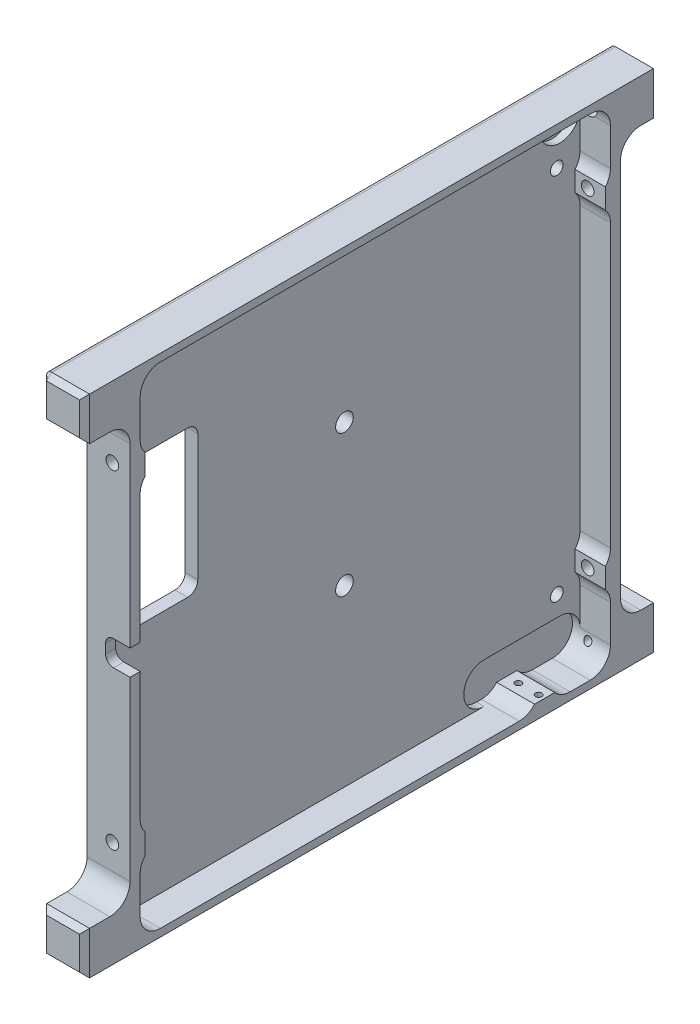
SolidWorks part; units mm, degrees
material "6061-T6 (SS)"
ref_plane "Front" through (0, 0, 0) normal (0, 0, 1) x (1, 0, 0)
ref_plane "Top" through (0, 0, 0) normal (0, 1, 0) x (1, 0, 0)
ref_plane "Right" through (0, 0, 0) normal (1, 0, 0) x (0, 0, -1)
sketch "Sketch1" plane through (0, 0, 0) normal (1, 0, 0) x (0, 0, -1)
  line L1 (0, 0) -> (-113.5, 0)
  line L2 (0, 0) -> (0, 100)
  line L3 (0, 100) -> (-113.5, 100)
  line L4 (-113.5, 0) -> (-113.5, 100)
  line L5 (-113.5, 91.5) -> (-104.5, 91.5)
  line L6 (-113.5, 91.5) -> (-113.5, 8.5)
  line L7 (-113.5, 8.5) -> (-104.5, 8.5)
  line L8 (-104.5, 91.5) -> (-104.5, 8.5)
  line L9 (0, 91.5) -> (-7.5, 91.5)
  line L10 (0, 91.5) -> (0, 8.5)
  line L11 (0, 8.5) -> (-7.5, 8.5)
  line L12 (-7.5, 91.5) -> (-7.5, 8.5)
  line L13 (-96.5, 91.5) -> (-15.5, 91.5)
  line L14 (-96.5, 91.5) -> (-96.5, 8.5)
  line L15 (-96.5, 8.5) -> (-15.5, 8.5)
  line L16 (-15.5, 91.5) -> (-15.5, 8.5)
  dimension "D1" = 113.5
  dimension "D2" = 100
  dimension "D3" = 8.5
  dimension "D4" = 8.5
  dimension "D5" = 8
  dimension "D6" = 8
  dimension "D7" = 9
  dimension "D8" = 7.5
extrude "Body" add sketch "Sketch1" along normal blind 8.5 contours L12 L9 L2 L3 L4 L5 L8 L7 L1 L11 L13 L16 L15 L14
fillet "RailFillet" radius 1 2 edges at (0, 0, 56.75) (0, 100, 56.75)
chamfer "FootChamfer" distance 1 angle 45 20 edges at (4.75, 0, 0) (8.5, 4.25, 0) (4.25, 8.5, 0) (0, 4.75, 0) (4.25, 91.5, 0) (8.5, 95.75, 0) (4.75, 100, 0) (0, 95.25, 0) (4.75, 100, 113.5) (8.5, 95.75, 113.5) (4.25, 91.5, 113.5) (0, 95.25, 113.5) (4.25, 8.5, 113.5) (8.5, 4.25, 113.5) (4.75, 0, 113.5) (0, 4.75, 113.5) (0.2929, 0.2929, 0) (0.2929, 99.7071, 0) (0.2929, 99.7071, 113.5) (0.2929, 0.2929, 113.5)
sketch "Sketch5" plane through (8.5, 0, 0) normal (1, 0, 0) x (0, 0, -1)
  line L1 (-96.5, 91.5) -> (-15.5, 91.5)
  line L2 (-96.5, 91.5) -> (-96.5, 8.5)
  line L3 (-96.5, 8.5) -> (-15.5, 8.5)
  line L4 (-15.5, 91.5) -> (-15.5, 8.5)
extrude "Boss-Extrude3" add sketch "Sketch5" against normal up to surface (8.5 mm away) up to face at (0, 50, 56.5)
sketch "Sketch6" plane through (8.5, 0, 0) normal (1, 0, 0) x (0, 0, -1)
  line L0 (-1, 100) -> (-112.5, 100) construction
  line L1 (-102.5, 98.5) -> (-9.5, 98.5)
  line L2 (-102.5, 98.5) -> (-102.5, 1.5)
  line L3 (-102.5, 1.5) -> (-9.5, 1.5)
  line L4 (-9.5, 98.5) -> (-9.5, 1.5)
  line L5 (-1, 0) -> (-112.5, 0) construction
  line L7 (-7.5, 91.5) -> (-7.5, 8.5) construction
  line L10 (-104.5, 91.5) -> (-104.5, 8.5) construction
  dimension "D1" = 1.5
  dimension "D2" = 1.5
  dimension "D3" = 2
  dimension "D4" = 2
extrude "Cut-Extrude3" cut sketch "Sketch6" against normal offset from surface (6 mm away) 2.5 up to face at (0, 50, 56.5)
sketch "Sketch4" plane through (8.5, 0, 0) normal (1, 0, 0) x (0, 0, -1)
  line L1 (-92.5, 90) -> (-19.5, 90)
  line L2 (-92.5, 90) -> (-92.5, 10)
  line L3 (-92.5, 10) -> (-19.5, 10)
  line L4 (-19.5, 90) -> (-19.5, 10)
  line L6 (-7.5, 91.5) -> (-7.5, 8.5) construction
  line L8 (-1, 100) -> (-112.5, 100) construction
  line L9 (-1, 0) -> (-112.5, 0) construction
  line L10 (-104.5, 91.5) -> (-104.5, 8.5) construction
  dimension "D1" = 12
  dimension "D2" = 10
  dimension "D3" = 10
  dimension "D4" = 12
ref_plane "Plane1" through (0, 50, 0) normal (0, 1, 0) x (1, 0, 0)
ref_plane "Plane2" through (0, 0, 56) normal (0, 0, -1) x (-1, 0, 0)
sketch "Sketch21" plane through (0, 0, 0) normal (1, 0, 0) x (0, 0, -1)
  line L0 (-98.1, 86.5) -> (-98.1, 13.5) construction
  line L1 (-98.1, 13.5) -> (-14.1, 13.5) construction
  line L2 (-14.1, 13.5) -> (-14.1, 86.5) construction
  line L3 (-14.1, 86.5) -> (-98.1, 86.5) construction
  line L4 (-14.1, 50) -> (-7.5, 50) construction
  line L6 (-7.5, 91.5) -> (-7.5, 8.5) construction
  line L7 (0, 99) -> (0, 92.5) construction
  line L8 (-14.1, 50) -> (-98.1, 50) construction
  line L9 (-56.1, 50) -> (-56.1, 36) construction
  line L10 (-7.5, 50) -> (-7.5, 0) construction
  line L11 (-112.5, 0) -> (-1, 0) construction
  line L12 (-1, 100) -> (-112.5, 100) construction
  line L13 (-7.5, 100) -> (-7.5, 50) construction
  line L16 (-56.1, 64) -> (-56.1, 50) construction
  point P3 (-14.1, 13.5)
  point P5 (-98.1, 86.5)
  point P7 (-98.1, 13.5)
  point P11 (-56.1, 36)
  point P25 (-14.1, 86.5)
  point P26 (-56.1, 64)
  dimension "D3" = 28
  dimension "D1" = 73
  dimension "D2" = 84
  dimension "D4" = 14.1
sketch "Sketch29" plane through (0, 0, 0) normal (0, 0, -1) x (-1, 0, 0)
  line L0 (-1, 92.5) -> (-7.5, 99)
  line L1 (-7.5, 99) -> (-1, 99)
  line L2 (-1, 99) -> (-4.25, 95.75)
hole_wizard "#8-36 Tapped Hole1" positions "Sketch30" profile "Sketch31" tap size "#8-36" standard "ANSI Inch"
sketch "Sketch30" plane through (0, 0, 0) normal (0, 0, -1) x (-1, 0, 0)
  point P0 (-4.25, 95.75)
sketch "Sketch31" plane through (4.25, 95.75, 0) normal (1, 0, 0) x (0, 1, 0)
  line L0 (0, 0) -> (0, 14.5878)
  line L1 (0, 14.5878) -> (1.7272, 13.55)
  line L2 (1.7272, 13.55) -> (1.7272, 0)
  line L5 (1.7272, 0) -> (0, 0)
  line L10 (0, 14.5878) -> (-1.7272, 13.55) construction
  line L11 (0, -6.35) -> (0, 107.95) construction
  dimension "Tap Drill Dia." = 3.4544
  dimension "Tap Drill Depth" = 13.55
  dimension "Drill Angle" = 118
cosmetic thread "Hole Thread1" parameters "D1"=10.5229, "D2"=4.1656
sketch "Sketch32" plane through (0, 0, 0) normal (0, 0, -1) x (-1, 0, 0)
  line L1 (-4.25, 1) -> (-4.25, 4.25) construction
  line L2 (-7.5, 1) -> (-1, 1) construction
  line L3 (-4.25, 4.25) -> (-7.5, 4.25) construction
  line L4 (-7.5, 7.5) -> (-7.5, 1) construction
  point P1 (-4.25, 4.25)
hole_wizard "#8-36 Tapped Hole2" [suppressed] positions "Sketch33" profile "Sketch34" tap size "#8-36" standard "ANSI Inch"
sketch "Sketch33" plane through (0, 0, 0) normal (0, 0, -1) x (-1, 0, 0)
  point P0 (-4.25, 4.25)
sketch "Sketch34" plane through (4.25, 4.25, 0) normal (1, 0, 0) x (0, 1, 0)
  line L0 (0, 0) -> (0, 11.4878)
  line L1 (0, 11.4878) -> (1.7272, 10.45)
  line L2 (1.7272, 10.45) -> (1.7272, 0)
  line L5 (1.7272, 0) -> (0, 0)
  line L10 (0, 11.4878) -> (-1.7272, 10.45) construction
  line L11 (0, -6.35) -> (0, 107.95) construction
  dimension "Tap Drill Dia." = 3.4544
  dimension "Tap Drill Depth" = 10.45
  dimension "Drill Angle" = 118
cosmetic thread "Hole Thread2" [suppressed] parameters "D1"=8.33, "D2"=4.1656
sketch "Sketch44" [suppressed] plane through (2.5, 0, 0) normal (1, 0, 0) x (0, 0, -1)
  point P0 (-17.45, 3.7)
  point P2 (-17.45, 7.7)
sketch "Sketch57" plane through (2.5, 0, 0) normal (1, 0, 0) x (0, 0, -1)
  line L0 (-9.5, 1.5) -> (-9.5, 98.5) construction
  line L1 (-9.5, 84.5) -> (-10.5, 84.5)
  line L2 (-9.5, 84.5) -> (-9.5, 80.5)
  line L3 (-9.5, 80.5) -> (-10.5, 80.5)
  line L4 (-10.5, 84.5) -> (-10.5, 80.5)
  line L5 (-102.5, 1.5) -> (-102.5, 98.5) construction
  line L6 (-9.5, 19.5) -> (-10.5, 19.5)
  line L7 (-9.5, 19.5) -> (-9.5, 15.5)
  line L8 (-9.5, 15.5) -> (-10.5, 15.5)
  line L9 (-10.5, 19.5) -> (-10.5, 15.5)
  line L10 (-10.5, 19.5) -> (-101.5, 19.5)
  line L11 (-10.5, 19.5) -> (-10.5, 15.5)
  line L12 (-10.5, 15.5) -> (-101.5, 15.5)
  line L13 (-101.5, 19.5) -> (-101.5, 15.5)
  line L14 (-10.5, 84.5) -> (-101.5, 84.5)
  line L15 (-10.5, 84.5) -> (-10.5, 80.5)
  line L16 (-10.5, 80.5) -> (-101.5, 80.5)
  line L17 (-101.5, 84.5) -> (-101.5, 80.5)
  line L18 (-101.5, 84.5) -> (-102.5, 84.5)
  line L19 (-101.5, 84.5) -> (-101.5, 80.5)
  line L20 (-101.5, 80.5) -> (-102.5, 80.5)
  line L21 (-102.5, 84.5) -> (-102.5, 80.5)
  line L22 (-9.5, 50) -> (-102.5, 50) construction
  line L23 (-101.5, 19.5) -> (-102.5, 19.5)
  line L24 (-101.5, 19.5) -> (-101.5, 15.5)
  line L25 (-101.5, 15.5) -> (-102.5, 15.5)
  line L26 (-102.5, 19.5) -> (-102.5, 15.5)
  line L28 (-102.5, 82.5) -> (-102.5, 50) construction
  line L29 (-102.5, 50) -> (-102.5, 17.5) construction
  line L31 (-9.5, 98.5) -> (-9.5, 1.5) construction
  dimension "D1" = 4
  dimension "D2" = 4
  dimension "D3" = 1
  dimension "D4" = 32.5
  dimension "D5" = 32.5
extrude "Boss-Extrude24" add sketch "Sketch57" along normal up to surface (6 mm away) contours L18 L21 L20 L17 | L23 L26 L25 L13 | L6 L9 L8 L7 | L1 L4 L3 L2 up to face at (8.5, 50, 56)
fillet "Fillet5" radius 4 8 edges at (5.5, 84.5, 102.5) (5.5, 19.5, 102.5) (5.5, 80.5, 102.5) (5.5, 15.5, 102.5) (5.5, 19.5, 9.5) (5.5, 15.5, 9.5) (5.5, 80.5, 9.5) (5.5, 84.5, 9.5)
sketch "Sketch59" plane through (0, 0, 7.5) normal (0, 0, -1) x (-1, 0, 0)
  line L0 (-5, 91.5) -> (-5, 82.5) construction
  line L2 (-5, 82.5) -> (-5, 17.5) construction
  line L3 (-5, 17.5) -> (-5, 8.5) construction
  line L5 (0, 91.5) -> (0, 8.5) construction
  line L6 (-8.5, 91.5) -> (0, 91.5) construction
  line L7 (-8.5, 8.5) -> (0, 8.5) construction
  dimension "D1" = 65
  dimension "D2" = 5
hole_wizard "M3x0.5 Tapped Hole1" positions "Sketch60" profile "Sketch61" tap size "M3x0.5" standard "ANSI Metric" end condition through all
sketch "Sketch60" plane through (0, 0, 7.5) normal (0, 0, -1) x (-1, 0, 0)
  point P0 (-5, 82.5)
  point P3 (-5, 17.5)
sketch "Sketch61" plane through (5, 82.5, 7.5) normal (1, 0, 0) x (0, 1, 0)
  line L0 (0, 0) -> (0, 106)
  line L1 (0, 106) -> (1.25, 106)
  line L2 (1.25, 106) -> (1.25, 0)
  line L5 (1.25, 0) -> (0, 0)
  line L11 (0, -6.35) -> (0, 107.95) construction
  dimension "Thru Tap Drill Dia." = 2.5
  dimension "Thru Tap Drill Depth" = 106
cosmetic thread "Hole Thread5" parameters "D2"=3
cosmetic thread "Hole Thread6" parameters "D2"=3
sketch "Sketch62" [suppressed] plane through (1, 0, 0) normal (1, 0, 0) x (0, 0, -1)
  line L1 (-11.25, 13.5) -> (-11.25, 1.5)
  line L2 (-11.5, 1.5) -> (-100, 1.5) construction
  line L3 (-11.25, 1.5) -> (-15.75, 1.5)
  line L4 (-15.75, 1.5) -> (-15.75, 10.1459)
  circle A0 centre (-14.75, 86.5) radius 3.5
  circle A1 centre (-14.75, 13.5) radius 3.5
  circle A2 centre (-97.75, 13.5) radius 3.5
  circle A3 centre (-97.75, 86.5) radius 3.5
  circle A4 centre (-97.75, 86.5) radius 1.25 construction
  circle A5 centre (-97.75, 13.5) radius 1.25 construction
  circle A6 centre (-14.75, 13.5) radius 1.25 construction
  circle A7 centre (-14.75, 86.5) radius 1.25 construction
  circle A8 centre (-97.75, 86.5) radius 1.25
  circle A9 centre (-97.75, 13.5) radius 1.25
  circle A10 centre (-14.75, 13.5) radius 1.25
  circle A11 centre (-14.75, 86.5) radius 1.25
  dimension "D1" = 7
  dimension "D2" = 4.5
fillet "Fillet7" radius 4 4 edges at (5.5, 98.5, 102.5) (5.5, 1.5, 102.5) (5.5, 1.5, 9.5) (5.5, 98.5, 9.5)
hole_wizard "M3x0.5 Tapped Hole2" positions "Sketch67" profile "Sketch68" tap size "M3x0.5" standard "ANSI Metric"
sketch "Sketch67" plane through (0, 0, 0) normal (-1, 0, 0) x (0, 0, 1)
  point P0 (14.1, 13.5)
  point P3 (14.1, 86.5)
  point P12 (98.1, 86.5)
  point P15 (98.1, 13.5)
sketch "Sketch68" plane through (0, 13.5, 14.1) normal (0, 1, 0) x (0, 0, 1)
  line L0 (0, 0) -> (0, 8.2511)
  line L1 (0, 8.2511) -> (1.25, 7.5)
  line L2 (1.25, 7.5) -> (1.25, 0)
  line L5 (1.25, 0) -> (0, 0)
  line L10 (0, 8.2511) -> (-1.25, 7.5) construction
  line L11 (0, -6.35) -> (0, 107.95) construction
  dimension "Tap Drill Dia." = 2.5
  dimension "Tap Drill Depth" = 7.5
  dimension "Drill Angle" = 118
cosmetic thread "Hole Thread17" parameters "D1"=2.5, "D2"=3
cosmetic thread "Hole Thread18" parameters "D1"=2.5, "D2"=3
cosmetic thread "Hole Thread21" parameters "D1"=2.5, "D2"=3
cosmetic thread "Hole Thread22" parameters "D1"=2.5, "D2"=3
fillet "Fillet8" radius 4 4 edges at (4.25, 8.5, 104.5) (4.25, 91.5, 104.5) (4.25, 8.5, 7.5) (4.25, 91.5, 7.5)
sketch "Sketch70" plane through (2.5, 0, 0) normal (1, 0, 0) x (0, 0, -1)
  line L0 (-13.5, 1.5) -> (-98.5, 1.5) construction
  line L2 (-13.5, 9.5) -> (-28.5, 9.5)
  line L4 (-13.5, 5.5) -> (-28.5, 5.5) construction
  line L5 (-28.5, 1.5) -> (-13.5, 1.5)
  circle A0 centre (-13.5, 94.5) radius 4
  arc A1 (-9.5, 94.5) -> (-13.5, 98.5) centre (-13.5, 94.5) ccw construction
  circle A2 centre (-13.5, 5.5) radius 4
  circle A3 centre (-28.5, 5.5) radius 4
  dimension "D1" = 15
extrude "Cut-Extrude14" cut sketch "Sketch70" against normal blind 1.5
sketch "Sketch75" plane through (0, 1.5, 0) normal (0, 1, 0) x (1, 0, 0)
  line L0 (1, -28.5) -> (1, -13.5) construction
  line L1 (1, -20.5) -> (8.5, -20.5)
  line L2 (1, -20.5) -> (1, -24.5)
  line L3 (1, -24.5) -> (8.5, -24.5)
  line L4 (8.5, -20.5) -> (8.5, -24.5)
  line L5 (8.5, -98.5) -> (8.5, -13.5) construction
  line L6 (8.5, -13.5) -> (1, -13.5) construction
  dimension "D1" = 7
  dimension "D2" = 4
extrude "Boss-Extrude25" add sketch "Sketch75" along normal blind 1.4
sketch "Sketch71" plane through (0, 2.9, 0) normal (0, 1, 0) x (1, 0, 0)
  line L0 (3.3, -22.5) -> (7.3, -22.5) construction
  line L1 (1, -28.5) -> (1, -24.5) construction
  dimension "D1" = 4
  dimension "D2" = 2.3
  dimension "D3" = 9
hole_wizard "M1.6x0.35 Tapped Hole1" positions "Sketch72" profile "Sketch73" tap size "M1.6x0.35" standard "ANSI Metric"
sketch "Sketch72" plane through (0, 2.9, 0) normal (0, 1, 0) x (1, 0, 0)
  point P0 (3.3, -22.5)
  point P3 (7.3, -22.5)
sketch "Sketch73" plane through (3.3, 2.9, 22.5) normal (1, 0, 0) x (0, 0, 1)
  line L0 (0, 0) -> (0, 4.6255)
  line L1 (0, 4.6255) -> (0.625, 4.25)
  line L2 (0.625, 4.25) -> (0.625, 0)
  line L5 (0.625, 0) -> (0, 0)
  line L10 (0, 4.6255) -> (-0.625, 4.25) construction
  line L11 (0, -6.35) -> (0, 107.95) construction
  dimension "Tap Drill Dia." = 1.25
  dimension "Tap Drill Depth" = 4.25
  dimension "Drill Angle" = 118
cosmetic thread "Hole Thread15" parameters "D1"=1.5, "D2"=1.6
cosmetic thread "Hole Thread16" parameters "D1"=1.5, "D2"=1.6
fillet "Fillet9" radius 4 2 edges at (4.75, 1.5, 24.5) (4.75, 1.5, 20.5)
sketch "Sketch76" plane through (0, 0, 0) normal (0, 0, -1) x (-1, 0, 0)
  line L0 (-1, 7.5) -> (-7.5, 1) construction
  point P4 (-4.25, 4.25)
hole_wizard "Ø1.5mm Dowel Hole1" positions "Sketch77" profile "Sketch79" hole size "Ø1.5" standard "ANSI Metric" end condition up to next
sketch "Sketch77" plane through (0, 0, 0) normal (0, 0, -1) x (-1, 0, 0)
  point P0 (-4.25, 4.25)
sketch "Sketch79" plane through (4.25, 4.25, 0) normal (1, 0, 0) x (0, 1, 0)
  line L0 (0, 0) -> (0, 9.7003)
  line L1 (0, 9.7003) -> (0.75, 9.7003)
  line L2 (0.75, 9.7003) -> (0.75, 0)
  line L5 (0.75, 0) -> (0, 0)
  line L11 (0, -6.35) -> (0, 107.95) construction
  dimension "Thru Hole Dia." = 1.5
  dimension "Thru Hole Depth" = 9.7003
sketch "Sketch81" plane through (2.5, 0, 0) normal (1, 0, 0) x (0, 0, -1)
  line L0 (-87.1, 51.5) -> (-87.1, 76.5) construction
  line L1 (-89.1, 51.5) -> (-89.1, 76.5)
  line L2 (-85.1, 51.5) -> (-85.1, 76.5)
  line L3 (-100.5, 51.5) -> (-100.5, 76.5) construction
  line L4 (-102.5, 51.5) -> (-102.5, 76.5)
  line L5 (-98.5, 51.5) -> (-98.5, 76.5)
  line L6 (-87.1, 51.5) -> (-100.5, 51.5) construction
  line L7 (-87.1, 49.5) -> (-100.5, 49.5)
  line L8 (-87.1, 76.5) -> (-100.5, 76.5) construction
  line L9 (-87.1, 78.5) -> (-100.5, 78.5)
  line L10 (-102.5, 22.1458) -> (-102.5, 77.8542) construction
  arc A0 (-89.1, 51.5) -> (-85.1, 51.5) centre (-87.1, 51.5) ccw
  arc A1 (-85.1, 76.5) -> (-89.1, 76.5) centre (-87.1, 76.5) ccw
  arc A2 (-102.5, 51.5) -> (-98.5, 51.5) centre (-100.5, 51.5) ccw
  arc A3 (-98.5, 76.5) -> (-102.5, 76.5) centre (-100.5, 76.5) ccw
  circle A6 centre (-98.1, 86.5) radius 1.25 construction
  point P2 (-87.1, 64)
  point P7 (-100.5, 64)
  line M19 (-102.5, 77.8542) -> (-102.5, 22.1458)
  dimension "D2" = 2
  dimension "D3" = 2
  dimension "D5" = 10
  dimension "D1" = 11
  dimension "D4" = 25
extrude "Cut-Extrude15" cut sketch "Sketch81" against normal through all contours L5 A3 A2 M19 | L2 A1 L1 A0 | A3 L5 A2 L7 A0 L1 A1 L9
sketch "Sketch84" plane through (0, 0, 0) normal (-1, 0, 0) x (0, 0, 1)
  line L0 (112.5, 0) -> (1, 0) construction
  line L1 (7.5, 87.5) -> (7.5, 12.5) construction
  circle A0 centre (56.1, 36) radius 1.75
  circle A1 centre (56.1, 64) radius 1.75
  dimension "D1" = 3.5
  dimension "D4" = 64
  dimension "D2" = 36
  dimension "D3" = 48.6
extrude "Cut-Extrude17" cut sketch "Sketch84" against normal through all
sketch "Sketch85" plane through (0, 0, 104.5) normal (0, 0, 1) x (1, 0, 0)
  line L0 (8.5, 50) -> (-8.6319, 50) construction
  line L1 (8.5, 87.5) -> (8.5, 12.5) construction
  line L6 (5.25, 47.5) -> (8.5, 47.5)
  line L7 (8.5, 47.5) -> (8.5, 52.5)
  line L8 (8.5, 52.5) -> (5.25, 52.5)
  line L9 (3.66, 49.09) -> (3.66, 50.91)
  arc A1 (3.66, 50.91) -> (5.25, 52.5) centre (5.25, 50.91) cw
  arc A2 (3.66, 49.09) -> (5.25, 47.5) centre (5.25, 49.09) ccw
  dimension "D1" = 1.59
  dimension "D4" = 3.25
  dimension "D2" = 5
  dimension "D3" = 2.5
extrude "Cut-Extrude18" cut sketch "Sketch85" against normal up to surface (2 mm away) up to face at (3.375, 57, 102.5)
